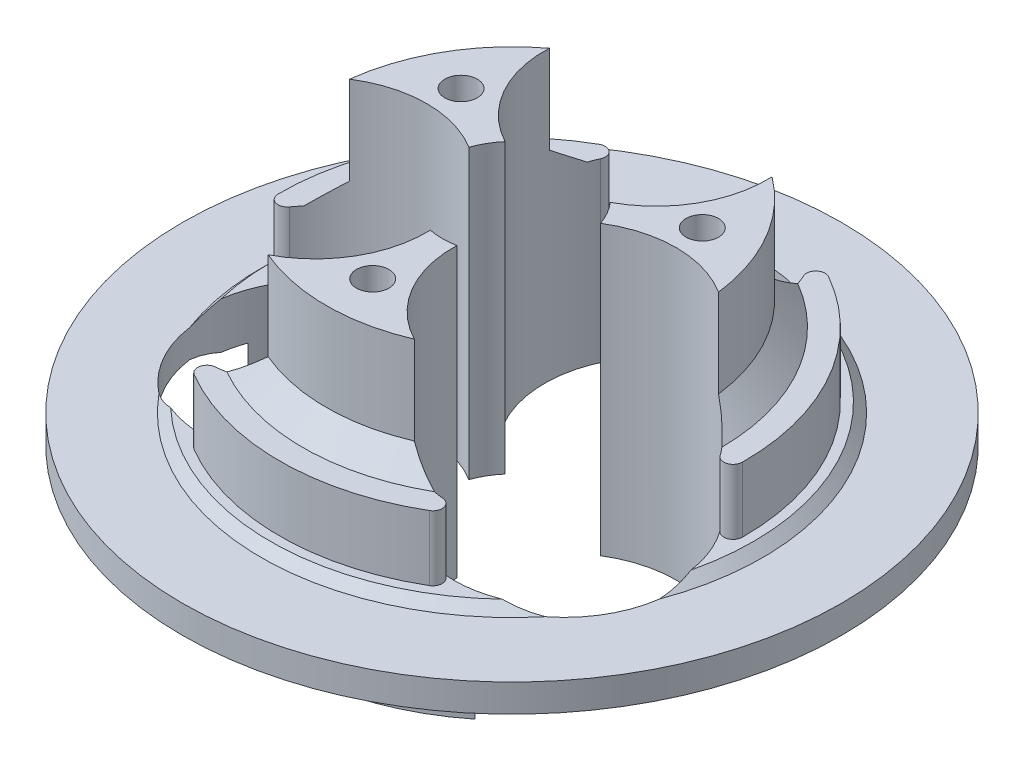
SolidWorks part; units mm, degrees
ref_plane "Front Plane" through (0, 0, 0) normal (0, 0, 1) x (1, 0, 0)
ref_plane "Top Plane" through (0, 0, 0) normal (0, 1, 0) x (1, 0, 0)
ref_plane "Right Plane" through (0, 0, 0) normal (1, 0, 0) x (0, 0, -1)
sketch "Sketch1" plane through (0, 0, 0) normal (0, 1, 0) x (1, 0, 0)
  circle A0 centre (0, 0) radius 35.5
  dimension "D1" = 71
extrude "Boss-Extrude1" add sketch "Sketch1" along normal mid plane 3
sketch "Sketch2" plane through (0, 1.5, 0) normal (0, 1, 0) x (1, 0, 0)
  circle A0 centre (0, 0) radius 26
  dimension "D1" = 52
extrude "Boss-Extrude2" add sketch "Sketch2" along normal blind 1
sketch "Sketch3" plane through (0, 2.5, 0) normal (0, 1, 0) x (1, 0, 0)
  circle A0 centre (0, 0) radius 25
  dimension "D1" = 50
extrude "Boss-Extrude3" add sketch "Sketch3" along normal blind 19
sketch "Sketch4" plane through (0, 21.5, 0) normal (0, 1, 0) x (1, 0, 0)
  line L0 (0, 15.5) -> (0, 0) construction
  line L1 (0, 0) -> (-13.4234, -7.75) construction
  circle A0 centre (0, 15.5) radius 12
  circle A1 centre (13.4234, -7.75) radius 12
  circle A2 centre (-13.4234, -7.75) radius 12
  dimension "D1" = 24
  dimension "D2" = 15.5
  dimension "D3" = 3
extrude "Cut-Extrude1" cut sketch "Sketch4" against normal through all
sketch "Sketch5" plane through (0, 21.5, 0) normal (0, 1, 0) x (1, 0, 0)
  circle A0 centre (0, 0) radius 7.5
  dimension "D1" = 15
extrude "Cut-Extrude2" cut sketch "Sketch5" against normal through all
fillet "Fillet1" radius 1 6 edges at (24.7231, 12, 3.7106) (9.1481, 12, -23.2661) (-9.1481, 12, -23.2661) (-24.7231, 12, 3.7106) (-15.575, 12, 19.5555) (15.575, 12, 19.5555)
sketch "Sketch6" plane through (0, 21.5, 0) normal (0, 1, 0) x (1, 0, 0)
  circle A0 centre (0, 0) radius 30.0189
  circle A1 centre (0, 0) radius 20
  dimension "D1" = 40
extrude "Cut-Extrude3" cut sketch "Sketch6" against normal blind 12
chamfer "Chamfer2" distance 2.5 angle 45 3 edges at (17.3205, 9.5, -10) (-17.3205, 9.5, -10) (0, 9.5, 20)
sketch "Sketch8" plane through (0, -1.5, 0) normal (0, -1, 0) x (1, 0, 0)
  circle A0 centre (0, 0) radius 25
  dimension "D1" = 50
extrude "Boss-Extrude4" add sketch "Sketch8" along normal blind 8
sketch "Sketch10" plane through (0, -9.5, 0) normal (0, -1, 0) x (1, 0, 0)
  circle A0 centre (0, 0) radius 7.5
  dimension "D1" = 15
extrude "Cut-Extrude6" cut sketch "Sketch10" against normal through all
sketch "Sketch7" plane through (0, 21.5, 0) normal (0, 1, 0) x (1, 0, 0)
  circle A0 centre (0, -15) radius 1.75
  circle A1 centre (-12.9904, 7.5) radius 1.75
  circle A2 centre (12.9904, 7.5) radius 1.75
  dimension "D1" = 15
  dimension "D2" = 3.5
  dimension "D3" = 3
extrude "Cut-Extrude4" cut sketch "Sketch7" against normal through all
sketch "Sketch11" plane through (0, -1.5, 0) normal (0, -1, 0) x (1, 0, 0)
  circle A0 centre (0, 0) radius 26
  circle A1 centre (0, 0) radius 25 construction
  circle A2 centre (0, 0) radius 25
  dimension "D1" = 1
extrude "Boss-Extrude5" add sketch "Sketch11" along normal blind 1
sketch "Sketch9" plane through (0, -9.5, 0) normal (0, -1, 0) x (1, 0, 0)
  circle A0 centre (-13.4234, 7.75) radius 12
  circle A1 centre (13.4234, 7.75) radius 12
  circle A2 centre (0, -15.5) radius 12
  dimension "D1" = 24
  dimension "D2" = 3
extrude "Cut-Extrude5" cut sketch "Sketch9" against normal through all
chamfer "Chamfer1" distance 1 angle 45 6 edges at (22.5167, -1.5, -13) (0, -1.5, 26) (-22.5167, -1.5, -13) (-22.5167, 1.5, -13) (22.5167, 1.5, -13) (0, 1.5, 26)
